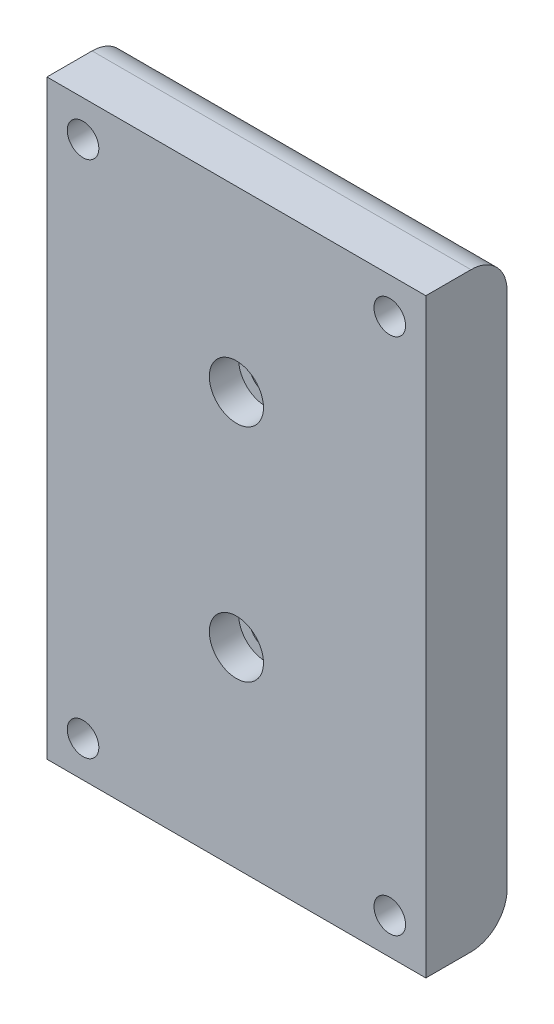
SolidWorks part; units mm, degrees
ref_plane "Front Plane" through (0, 0, 0) normal (0, 0, 1) x (1, 0, 0)
ref_plane "Top Plane" through (0, 0, 0) normal (0, 1, 0) x (1, 0, 0)
ref_plane "Right Plane" through (0, 0, 0) normal (1, 0, 0) x (0, 0, -1)
sketch "Sketch1" plane through (0, 0, 0) normal (0, 0, 1) x (1, 0, 0)
  line L1 (0, 0) -> (42, 0)
  line L2 (0, 0) -> (0, 65.5)
  line L3 (0, 65.5) -> (42, 65.5)
  line L4 (42, 0) -> (42, 65.5)
  dimension "D1" = 42
  dimension "D2" = 65.5
extrude "Boss-Extrude1" add sketch "Sketch1" along normal blind 9
sketch "Sketch2" plane through (0, 0, 0) normal (0, 0, -1) x (-1, 0, 0)
  line L0 (-42, 32.75) -> (0, 32.75) construction
  line L1 (-42, 0) -> (-42, 65.5) construction
  line L2 (0, 65.5) -> (0, 0) construction
  line L3 (-42, 45.75) -> (0, 45.75) construction
  line L4 (-21, 45.75) -> (-21, 21.25) construction
  line L5 (-25.5, 21.25) -> (-25.5, 35.0846)
  line L6 (-16.5, 21.25) -> (-16.5, 35.0846)
  arc A0 (-14.5556, 41.0098) -> (-27.4444, 41.0098) centre (-21, 45.75) ccw
  arc A1 (-25.5, 21.25) -> (-16.5, 21.25) centre (-21, 21.25) ccw
  arc A2 (-16.5, 35.0846) -> (-14.5556, 41.0098) centre (-6.5, 35.0846) cw
  arc A3 (-25.5, 35.0846) -> (-27.4444, 41.0098) centre (-35.5, 35.0846) ccw
  point P11 (-21, 45.75)
  dimension "D2" = 16
  dimension "D3" = 9
  dimension "D5" = 10
  dimension "D4" = 24.5
  dimension "D1" = 13
extrude "Cut-Extrude2" cut sketch "Sketch2" against normal blind 4.5
sketch "Sketch3" plane through (0, 0, 4.5) normal (0, 0, -1) x (-1, 0, 0)
  line L0 (-21, 45.75) -> (-21, 25.25) construction
  line L1 (-21, 25.25) -> (-21, 21.25) construction
  line L2 (-24, 21.25) -> (-24, 25.25)
  line L3 (-18, 25.25) -> (-18, 21.25)
  arc A0 (-18, 25.25) -> (-24, 25.25) centre (-21, 25.25) ccw
  arc A1 (-24, 21.25) -> (-18, 21.25) centre (-21, 21.25) ccw
  circle A2 centre (-21, 25.25) radius 1.75
  circle A3 centre (-21, 21.25) radius 1.75
  circle A4 centre (-21, 45.75) radius 1.75
  dimension "D2" = 6
  dimension "D4" = 3.5
  dimension "D5" = 3.5
  dimension "D1" = 20.5
  dimension "D3" = 4
extrude "Cut-Extrude5" cut sketch "Sketch3" against normal through all contours A3 | A4 region at (21, 21.25, 4.5) region at (21, 45.75, 4.5)
sketch "Sketch5" plane through (0, 0, 9) normal (0, 0, 1) x (1, 0, 0)
  circle A0 centre (21, 21.25) radius 3
  circle A1 centre (21, 45.75) radius 3
  dimension "D1" = 6
extrude "Cut-Extrude6" cut sketch "Sketch5" against normal blind 3.25
fillet "Fillet1" radius 4 2 edges at (21, 0, 0) (21, 65.5, 0)
sketch "Sketch6" plane through (0, 0, 0) normal (0, 0, -1) x (-1, 0, 0)
  line L0 (-4, 61.5) -> (-4, 4) construction
  line L1 (-42, 65.5) -> (0, 65.5) construction
  line L2 (-42, 65.5) -> (-42, 0) construction
  line L3 (-42, 0) -> (0, 0) construction
  line L4 (0, 65.5) -> (0, 0) construction
  line L5 (-38, 4) -> (-4, 4) construction
  line L6 (-38, 61.5) -> (-38, 4) construction
  line L7 (-38, 61.5) -> (-4, 61.5) construction
  circle A0 centre (-38, 61.5) radius 1.75
  circle A1 centre (-4, 61.5) radius 1.75
  circle A2 centre (-4, 4) radius 1.75
  circle A3 centre (-38, 4) radius 1.75
  line M16 (-42, 4) -> (0, 4)
  dimension "D2" = 3.5
  dimension "D1" = 4
extrude "Cut-Extrude7" cut sketch "Sketch6" against normal through all contours A2 M16 | A2 M16 | A3 M16 | A3 M16 | A0 | A1 region at (4, 4.7427, 0) region at (38, 3.2573, 0) region at (38, 4.7427, 0) region at (4, 3.2573, 0)
sketch "Sketch7" plane through (0, 0, 0) normal (0, 0, -1) x (-1, 0, 0)
  circle A0 centre (-38, 61.5) radius 3
  circle A1 centre (-4, 61.5) radius 3
  circle A2 centre (-4, 4) radius 3
  circle A3 centre (-38, 4) radius 3
  dimension "D1" = 6
extrude "Cut-Extrude8" cut sketch "Sketch7" against normal blind 3
